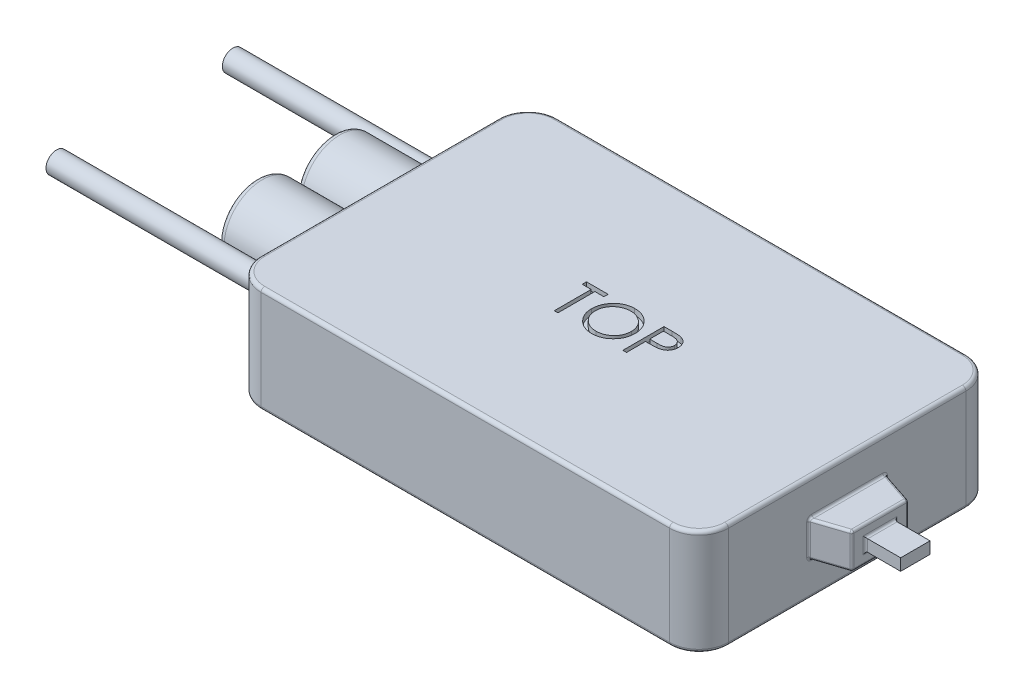
SolidWorks part; units mm, degrees
ref_plane "Front Plane" through (0, 0, 0) normal (0, 0, 1) x (1, 0, 0)
ref_plane "Top Plane" through (0, 0, 0) normal (0, 1, 0) x (1, 0, 0)
ref_plane "Right Plane" through (0, 0, 0) normal (1, 0, 0) x (0, 0, -1)
sketch "Sketch1" plane through (0, 0, 0) normal (0, 1, 0) x (1, 0, 0)
  line L0 (-19.875, 0) -> (19.875, 0) construction
  line L1 (-19.875, 12.6) -> (19.875, 12.6)
  line L2 (-19.875, 12.6) -> (-19.875, -12.6)
  line L3 (-19.875, -12.6) -> (19.875, -12.6)
  line L4 (19.875, 12.6) -> (19.875, -12.6)
  point P6 (0, 0)
  dimension "D1" = 39.75
  dimension "D2" = 25.2
extrude "Boss-Extrude1" add sketch "Sketch1" along normal blind 9
ref_plane "Plane4" through (0, 4.5, 0) normal (0, -1, 0) x (-1, 0, 0)
sketch "Sketch4" plane through (0, 4.5, 0) normal (0, -1, 0) x (-1, 0, 0)
  line L0 (28.8067, 0) -> (-28.8067, 0) construction
  line L1 (-19.875, 3.3) -> (-22.675, 2.375)
  line L2 (-19.875, -12.6) -> (-19.875, 12.6) construction
  line L3 (-22.675, 2.375) -> (-22.675, -2.375)
  line L4 (-19.875, -3.3) -> (-22.675, -2.375)
  line L5 (-19.875, 3.3) -> (-19.875, -3.3)
  point P9 (-22.675, 0)
  point P10 (-19.875, 0)
  dimension "D1" = 6.6
  dimension "D2" = 4.75
  dimension "D3" = 2.8
extrude "Boss-Extrude2" add sketch "Sketch4" along normal blind 1.5 and the other way blind 1.5
sketch "Sketch5" plane through (22.675, 0, 0) normal (1, 0, 0) x (0, 0, -1)
  line L0 (0, 0) -> (0, 9) construction
  line L1 (-1.25, 5) -> (1.25, 5)
  line L2 (-1.25, 5) -> (-1.25, 4)
  line L3 (-1.25, 4) -> (1.25, 4)
  line L4 (1.25, 5) -> (1.25, 4)
  line L5 (-12.6, 9) -> (12.6, 9) construction
  line L6 (-13.86, 4.5) -> (13.86, 4.5) construction
  point P9 (0, 5)
  point P10 (1.25, 4.5)
  dimension "D1" = 2.5
  dimension "D2" = 1
extrude "Boss-Extrude3" add sketch "Sketch5" along normal blind 3
sketch "Sketch6" plane through (-19.875, 0, 0) normal (-1, 0, 0) x (0, 0, 1)
  line L0 (-13.86, 4.5) -> (13.86, 4.5) construction
  line L1 (0, 10.8151) -> (0, -1.5476) construction
  circle A0 centre (-3.3, 4.5) radius 3.25
  circle A1 centre (3.3, 4.5) radius 3.25
  dimension "D1" = 6.5
  dimension "D2" = 6.6
extrude "Boss-Extrude5" add sketch "Sketch6" along normal blind 7.2
sketch "Sketch7" plane through (-19.875, 0, 0) normal (-1, 0, 0) x (0, 0, 1)
  line L0 (-13.86, 4.5) -> (13.86, 4.5) construction
  line L1 (0, 9) -> (0, 0) construction
  line L2 (-12.6, 9) -> (12.6, 9) construction
  circle A0 centre (-7.5, 4.5) radius 0.9
  circle A1 centre (7.5, 4.5) radius 0.9
  dimension "D1" = 1.8
  dimension "D2" = 7.5
extrude "Boss-Extrude6" add sketch "Sketch7" along normal blind 20
fillet "Fillet1" radius 2.5 4 edges at (19.875, 4.5, -12.6) (19.875, 4.5, 12.6) (-19.875, 4.5, 12.6) (-19.875, 4.5, -12.6)
fillet "Fillet2" radius 0.3 16 edges at (-19.1428, 0, -11.8678) (-19.875, 0, 0) (-19.1428, 0, 11.8678) (0, 0, 12.6) (19.1428, 0, 11.8678) (19.875, 0, 0) (19.1428, 0, -11.8678) (0, 0, -12.6) (19.1428, 9, 11.8678) (0, 9, 12.6) (-19.1428, 9, 11.8678) (-19.875, 9, 0) (-19.1428, 9, -11.8678) (0, 9, -12.6) (19.1428, 9, -11.8678) (19.875, 9, 0)
fillet "Fillet3" radius 0.5 2 edges at (-27.075, 4.5, -0.05) (-27.075, 4.5, 0.05)
fillet "Fillet4" radius 0.2 16 edges at (19.875, 6, 0) (19.875, 3, 0) (21.275, 6, -2.8375) (19.875, 4.5, -3.3) (21.275, 3, -2.8375) (21.275, 6, 2.8375) (21.275, 3, 2.8375) (19.875, 4.5, 3.3) (22.675, 4.5, -1.25) (22.675, 5, 0) (22.675, 4.5, 1.25) (22.675, 4, 0) (22.675, 6, 0) (22.675, 4.5, -2.375) (22.675, 3, 0) (22.675, 4.5, 2.375)
sketch "Sketch8" plane through (0, 9, 0) normal (0, 1, 0) x (1, 0, 0)
  text T0 "TOP"
extrude "Cut-Extrude1" cut sketch "Sketch8" against normal blind 0.5
